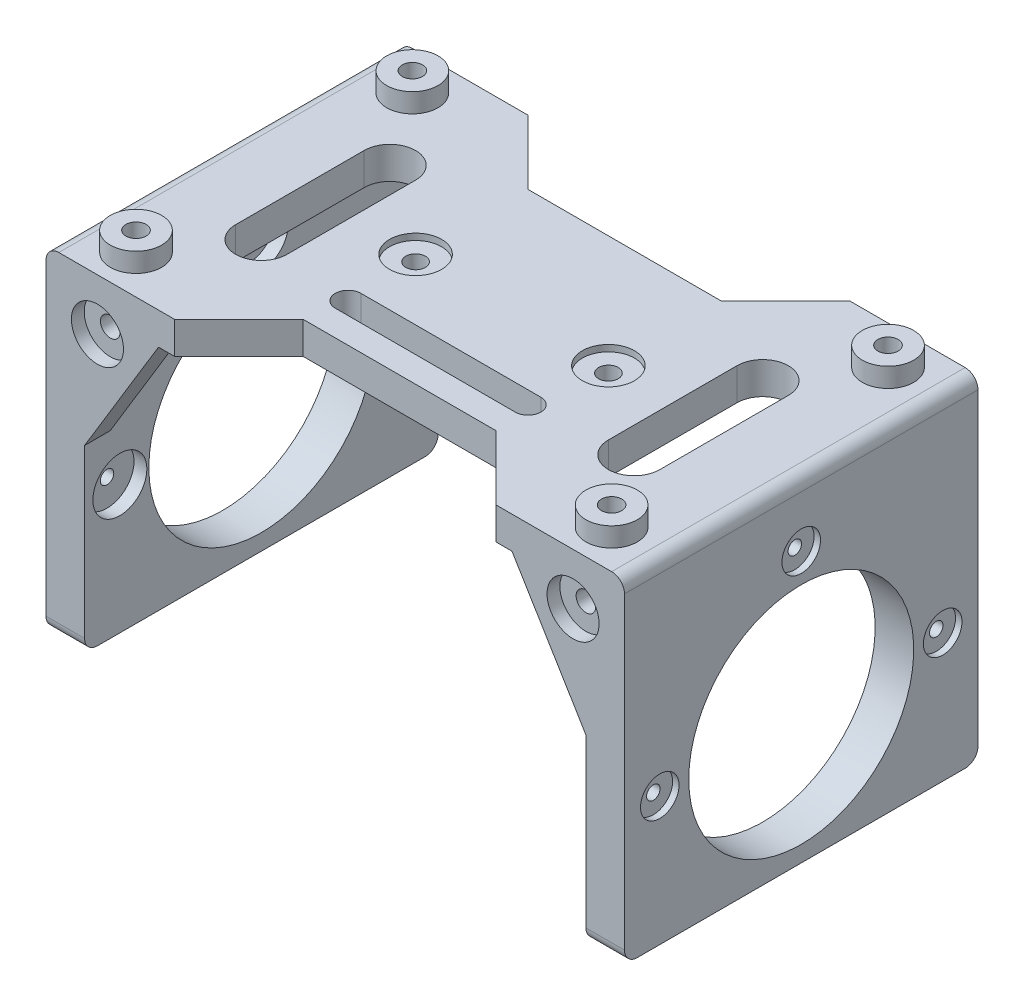
SolidWorks part; units mm, degrees
ref_plane "前视基准面" through (0, 0, 0) normal (0, 0, 1) x (1, 0, 0)
ref_plane "上视基准面" through (0, 0, 0) normal (0, 1, 0) x (1, 0, 0)
ref_plane "右视基准面" through (0, 0, 0) normal (1, 0, 0) x (0, 0, -1)
sketch "草图1" plane through (0, 0, 0) normal (0, 1, 0) x (1, 0, 0)
  line L0 (0, 0) -> (20, 0)
  line L9 (20, 0) -> (30, -10)
  line L10 (30, -10) -> (60, -10)
  line L11 (60, -10) -> (70, 0)
  line L12 (70, 0) -> (90, 0)
  line L13 (90, 0) -> (90, -55)
  line L14 (90, -55) -> (70, -55)
  line L15 (70, -55) -> (60, -45)
  line L16 (60, -45) -> (30, -45)
  line L17 (30, -45) -> (20, -55)
  line L18 (20, -55) -> (0, -55)
  line L19 (0, -55) -> (0, 0)
  dimension "D1" = 35
  dimension "D2" = 55
  dimension "D3" = 90
  dimension "D4" = 20
  dimension "D5" = 30
extrude "凸台-拉伸1" add sketch "草图1" along normal blind 52
sketch "草图2" plane through (0, 0, 55) normal (0, 0, 1) x (1, 0, 0)
  line L0 (6, 0) -> (6, 28)
  line L1 (6, 0) -> (84, 0)
  line L2 (0, 0) -> (20, 0) construction
  line L3 (6, 28) -> (17.5, 47)
  line L4 (17.5, 47) -> (72.5, 47)
  line L5 (72.5, 47) -> (84, 28)
  line L6 (84, 28) -> (84, 0)
  line L7 (70, 0) -> (90, 0) construction
  line L8 (0, 52) -> (0, 0) construction
  line L9 (90, 52) -> (90, 0) construction
  line L10 (30, 52) -> (60, 52) construction
  dimension "D1" = 6
  dimension "D2" = 6
  dimension "D3" = 5
  dimension "D4" = 55
  dimension "D6" = 28
extrude "切除-拉伸1" cut sketch "草图2" against normal through all
sketch "草图3" plane through (0, 47, 0) normal (0, -1, 0) x (1, 0, 0)
  line L0 (6, 51) -> (17.5, 51)
  line L1 (6, 0) -> (6, 55) construction
  line L2 (17.5, 0) -> (17.5, 55) construction
  line L3 (17.5, 51) -> (17.5, 4)
  line L4 (17.5, 4) -> (6, 4)
  line L5 (6, 4) -> (6, 51)
  line L6 (72.5, 0) -> (72.5, 55) construction
  line L7 (72.5, 51) -> (84, 51)
  line L8 (72.5, 51) -> (72.5, 4)
  line L9 (72.5, 4) -> (84, 4)
  line L10 (84, 51) -> (84, 4)
  line L11 (84, 0) -> (84, 55) construction
  line L12 (17.5, 55) -> (6, 55) construction
  line L13 (17.5, 0) -> (6, 0) construction
  line L14 (84, 55) -> (72.5, 55) construction
  line L15 (84, 0) -> (72.5, 0) construction
  dimension "D1" = 4
  dimension "D2" = 4
  dimension "D3" = 4
  dimension "D4" = 4
extrude "切除-拉伸2" cut sketch "草图3" along normal up to next
sketch "草图4" plane through (0, 52, 0) normal (0, 1, 0) x (1, 0, 0)
  line L0 (74, -37.5) -> (74, -17.5) construction
  line L1 (70, -37.5) -> (70, -17.5)
  line L2 (78, -37.5) -> (78, -17.5)
  line L3 (16, -37.5) -> (16, -17.5) construction
  line L4 (12, -37.5) -> (12, -17.5)
  line L5 (20, -37.5) -> (20, -17.5)
  line L6 (90, -27.5) -> (74, -27.5) construction
  line L7 (90, -55) -> (90, 0) construction
  line L8 (0, -27.5) -> (16, -27.5) construction
  line L9 (0, 0) -> (0, -55) construction
  line L10 (31, -39) -> (59, -39) construction
  line L11 (31, -37) -> (59, -37)
  line L12 (31, -41) -> (59, -41)
  line L13 (45, -39) -> (45, -45) construction
  line L14 (30, -45) -> (60, -45) construction
  arc A0 (70, -37.5) -> (78, -37.5) centre (74, -37.5) ccw
  arc A1 (78, -17.5) -> (70, -17.5) centre (74, -17.5) ccw
  arc A2 (12, -37.5) -> (20, -37.5) centre (16, -37.5) ccw
  arc A3 (20, -17.5) -> (12, -17.5) centre (16, -17.5) ccw
  arc A4 (31, -37) -> (31, -41) centre (31, -39) ccw
  arc A5 (59, -41) -> (59, -37) centre (59, -39) ccw
  point P2 (74, -27.5)
  point P9 (16, -27.5)
  point P24 (45, -39)
  dimension "D5" = 4
  dimension "D6" = 4
  dimension "D8" = 2
  dimension "D1" = 20
  dimension "D2" = 20
  dimension "D3" = 16
  dimension "D4" = 16
  dimension "D7" = 6
  dimension "D9" = 28
extrude "切除-拉伸3" cut sketch "草图4" against normal up to next
sketch "草图15" plane through (0, 52, 0) normal (0, 1, 0) x (1, 0, 0)
  line L0 (20, 0) -> (0, 0) construction
  line L1 (0, 0) -> (0, -55) construction
  line L2 (0, -55) -> (20, -55) construction
  line L3 (70, -55) -> (90, -55) construction
  line L4 (90, -55) -> (90, 0) construction
  line L5 (90, 0) -> (70, 0) construction
  circle A0 centre (8, -6) radius 4
  circle A1 centre (8, -6) radius 1.575
  circle A2 centre (82, -6) radius 4
  circle A3 centre (82, -6) radius 1.575
  circle A4 centre (82, -49) radius 4
  circle A5 centre (82, -49) radius 1.575
  circle A6 centre (8, -49) radius 4
  circle A7 centre (8, -49) radius 1.575
  dimension "D1" = 8
  dimension "D4" = 3.15
  dimension "D7" = 6
  dimension "D9" = 6
  dimension "D10" = 8
  dimension "D2" = 6
  dimension "D3" = 8
  dimension "D5" = 8
  dimension "D6" = 6
  dimension "D8" = 8
extrude "凸台-拉伸2" add sketch "草图15" along normal blind 3
sketch "草图5" plane through (0, 0, 0) normal (-1, 0, 0) x (0, 0, 1)
  line L0 (0, 0) -> (55, 0) construction
  line L1 (27.5, 0) -> (27.5, 20) construction
  circle A0 centre (27.5, 20) radius 17.5
  dimension "D2" = 35
  dimension "D1" = 20
extrude "切除-拉伸4" cut sketch "草图5" against normal through all
sketch "草图9" plane through (0, 0, 0) normal (-1, 0, 0) x (0, 0, 1)
  circle A0 centre (49.5078, 20) radius 4 construction
  circle A1 centre (5.4922, 20) radius 4 construction
  circle A2 centre (27.5, 42.0078) radius 4 construction
  circle A3 centre (49.5078, 20) radius 4
  circle A4 centre (5.4922, 20) radius 4
  circle A5 centre (27.5, 42.0078) radius 4
wrap "包覆2" sketch "草图9" wrap type scribe source sketch "草图9" face at (0, 20, 45)
sketch "草图10" plane through (0, 0, 0) normal (-1, 0, 0) x (0, 0, 1)
  line L0 (27.5, 20) -> (5.4922, 20) construction
  line L1 (27.5, 20) -> (27.5, 42.0078) construction
  circle A1 centre (5.4922, 20) radius 3
  circle A2 centre (27.5, 42.0078) radius 3
  circle A3 centre (49.5078, 20) radius 3
  dimension "D1" = 6
  dimension "D3" = 90
  dimension "D2" = 3
extrude "切除-拉伸5" cut sketch "草图10" against normal blind 1
sketch "草图11" plane through (6, 0, 0) normal (1, 0, 0) x (0, 0, -1)
  circle A0 centre (-49.5078, 20) radius 4 construction
  circle A1 centre (-5.4922, 20) radius 4 construction
  circle A2 centre (-27.5, 42.0078) radius 4 construction
  circle A3 centre (-49.5078, 20) radius 4 construction
  circle A4 centre (-5.4922, 20) radius 4 construction
  circle A5 centre (-27.5, 42.0078) radius 4 construction
  circle A6 centre (-49.5078, 20) radius 4.2
  circle A7 centre (-5.4922, 20) radius 4.2
  circle A8 centre (-27.5, 42.0078) radius 4.2
  dimension "D1" = 0.2
extrude "切除-拉伸6" cut sketch "草图11" against normal blind 2
sketch "草图12" plane through (90, 0, 0) normal (1, 0, 0) x (0, 0, -1)
  circle A0 centre (-49.5078, 20) radius 3 construction
  circle A1 centre (-5.4922, 20) radius 3 construction
  circle A2 centre (-27.5, 42.0078) radius 3 construction
  circle A3 centre (-49.5078, 20) radius 3
  circle A4 centre (-5.4922, 20) radius 3
  circle A5 centre (-27.5, 42.0078) radius 3
extrude "切除-拉伸7" cut sketch "草图12" against normal blind 1
sketch "草图13" plane through (84, 0, 0) normal (-1, 0, 0) x (0, 0, 1)
  circle A12 centre (49.5078, 20) radius 4 construction
  circle A13 centre (5.4922, 20) radius 4 construction
  circle A14 centre (27.5, 42.0078) radius 4 construction
  circle A15 centre (49.5078, 20) radius 4 construction
  circle A16 centre (5.4922, 20) radius 4 construction
  circle A17 centre (27.5, 42.0078) radius 4 construction
  circle A18 centre (49.5078, 20) radius 4.2
  circle A19 centre (5.4922, 20) radius 4.2
  circle A20 centre (27.5, 42.0078) radius 4.2
  dimension "D1" = 0.2
extrude "切除-拉伸8" cut sketch "草图13" against normal blind 2
sketch "草图14" plane through (89, 0, 0) normal (1, 0, 0) x (0, 0, -1)
  line L0 (-27.5, 20) -> (-49.5078, 20) construction
  line L1 (-27.5, 20) -> (-27.5, 42.0078) construction
  circle A1 centre (-49.5078, 20) radius 1.05
  circle A2 centre (-27.5, 42.0078) radius 1.05
  circle A3 centre (-5.4922, 20) radius 1.05
  dimension "D1" = 2.1
  dimension "D3" = 90
  dimension "D2" = 3
extrude "切除-拉伸9" cut sketch "草图14" against normal through all
sketch "草图17" plane through (0, 52, 0) normal (0, 1, 0) x (1, 0, 0)
  circle A0 centre (8, -49) radius 1.575 construction
  circle A1 centre (82, -49) radius 1.575 construction
  circle A2 centre (82, -6) radius 1.575 construction
  circle A3 centre (8, -6) radius 1.575 construction
  circle A4 centre (8, -49) radius 1.575
  circle A5 centre (82, -49) radius 1.575
  circle A6 centre (82, -6) radius 1.575
  circle A7 centre (8, -6) radius 1.575
extrude "切除-拉伸10" cut sketch "草图17" against normal through all
fillet "圆角2" radius 2 6 edges at (0, 52, 27.5) (90, 52, 27.5) (3, 0, 55) (3, 0, 0) (87, 0, 55) (87, 0, 0)
sketch "草图18" plane through (0, 0, 55) normal (0, 0, 1) x (1, 0, 0)
  line L0 (2, 52) -> (20, 52) construction
  line L2 (0, 50) -> (0, 2) construction
  line L3 (70, 52) -> (88, 52) construction
  line L4 (90, 50) -> (90, 2) construction
  circle A0 centre (8, 44) radius 1.525
  circle A1 centre (82, 44) radius 1.525
  dimension "D1" = 3.05
  dimension "D2" = 8
  dimension "D3" = 8
  dimension "D4" = 8
  dimension "D5" = 8
extrude "切除-拉伸11" cut sketch "草图18" against normal through all
sketch "草图19" plane through (0, 0, 55) normal (0, 0, 1) x (1, 0, 0)
  circle A0 centre (8, 44) radius 4.05
  circle A1 centre (82, 44) radius 4.05
  dimension "D1" = 8.1
extrude "切除-拉伸12" cut sketch "草图19" against normal blind 2
sketch "草图20" plane through (0, 0, 0) normal (0, 0, -1) x (-1, 0, 0)
  circle A0 centre (-82, 44) radius 4.05
  circle A1 centre (-8, 44) radius 4.05
  dimension "D1" = 8.1
extrude "切除-拉伸13" cut sketch "草图20" against normal blind 2
sketch "草图21" plane through (0, 52, 0) normal (0, 1, 0) x (1, 0, 0)
  line L0 (30, -10) -> (30, -27.5) construction
  line L1 (2, -27.5) -> (30, -27.5) construction
  line L2 (2, 0) -> (2, -55) construction
  line L3 (60, -10) -> (60, -27.5) construction
  line L4 (60, -27.5) -> (88, -27.5) construction
  line L5 (88, -55) -> (88, 0) construction
  circle A0 centre (30, -27.5) radius 1.525
  circle A2 centre (60, -27.5) radius 1.525
  dimension "D1" = 3.05
extrude "切除-拉伸14" cut sketch "草图21" against normal through all
sketch "草图22" plane through (0, 52, 0) normal (0, 1, 0) x (1, 0, 0)
  circle A0 centre (30, -27.5) radius 4.05
  circle A1 centre (60, -27.5) radius 4.05
  dimension "D1" = 8.1
extrude "切除-拉伸15" cut sketch "草图22" against normal blind 1
sketch "草图23" plane through (0, 47, 0) normal (0, -1, 0) x (1, 0, 0)
  circle A0 centre (30, 27.5) radius 4.05
  circle A1 centre (60, 27.5) radius 4.05
  dimension "D1" = 8.1
extrude "切除-拉伸16" cut sketch "草图23" against normal blind 1
